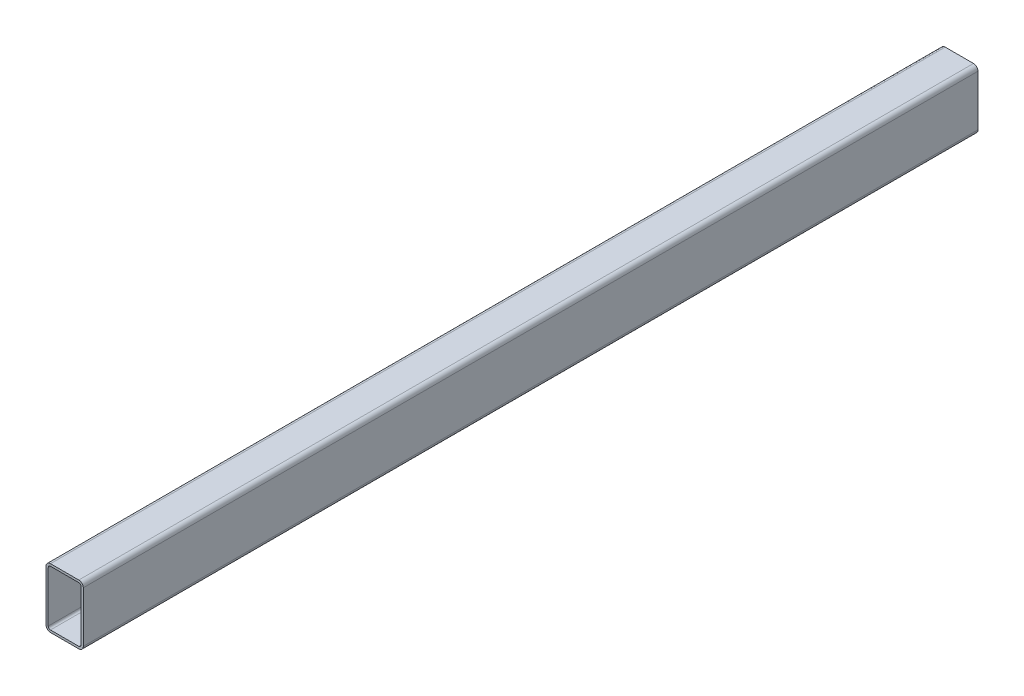
SolidWorks part; units mm, degrees
ref_plane "Front Plane" through (0, 0, 0) normal (0, 0, 1) x (1, 0, 0)
ref_plane "Top Plane" through (0, 0, 0) normal (0, 1, 0) x (1, 0, 0)
ref_plane "Right Plane" through (0, 0, 0) normal (1, 0, 0) x (0, 0, -1)
sketch "Sketch1" plane through (0, 0, 0) normal (0, 0, 1) x (1, 0, 0)
  line L0 (19, 37) -> (-19, 37)
  line L1 (19, -40) -> (-19, -40)
  line L2 (25, -34) -> (25, 34)
  line L3 (19, 40) -> (-19, 40)
  line L4 (-25, -34) -> (-25, 34)
  line L5 (25, -40) -> (-25, 40) construction
  line L6 (25, 40) -> (-25, -40) construction
  line L7 (-22, -34) -> (-22, 34)
  line L8 (19, -37) -> (-19, -37)
  line L9 (22, -34) -> (22, 34)
  arc A0 (-19, -40) -> (-25, -34) centre (-19, -34) cw
  arc A1 (19, -40) -> (25, -34) centre (19, -34) ccw
  arc A2 (25, 34) -> (19, 40) centre (19, 34) ccw
  arc A3 (-19, 40) -> (-25, 34) centre (-19, 34) ccw
  arc A4 (-19, 37) -> (-22, 34) centre (-19, 34) ccw
  arc A5 (-19, -37) -> (-22, -34) centre (-19, -34) cw
  arc A6 (19, -37) -> (22, -34) centre (19, -34) ccw
  arc A7 (22, 34) -> (19, 37) centre (19, 34) ccw
  point P0 (0, 0)
  dimension "D1" = 6
  dimension "D3" = 80
  dimension "D4" = 50
  dimension "D2" = 3
extrude "Boss-Extrude1" add sketch "Sketch1" along normal mid plane 1200
sketch "Sketch2" plane through (25, 0, 0) normal (1, 0, 0) x (0, 0, -1)
  line L0 (0, 197.5737) -> (0, -189.4858) construction
  line L1 (-600, -40) -> (600, -40) construction
  line L2 (-582, 22) -> (-568, 22) construction
  line L3 (-582, 22) -> (-582, -22) construction
  line L4 (-582, -22) -> (-568, -22) construction
  line L5 (-568, 22) -> (-568, -22) construction
  line L6 (-582, 22) -> (-568, -22) construction
  line L7 (-582, -22) -> (-568, 22) construction
  line L8 (-600, 40) -> (600, 40) construction
  line L9 (-582, 22) -> (-582, 40) construction
  line L10 (-582, 22) -> (-600, 22) construction
  line L11 (-600, -34) -> (-600, 34) construction
  line L12 (-600, 40) -> (-550, 40) construction
  line L13 (-600, 40) -> (-600, -40) construction
  line L14 (-600, -40) -> (-550, -40) construction
  line L15 (-550, 40) -> (-550, -40) construction
  line L16 (-575, -40) -> (-575, 40) construction
  line L17 (-600, 0) -> (-550, 0) construction
  circle A0 centre (-582, 22) radius 2.5
  circle A1 centre (-568, 22) radius 2.5
  circle A2 centre (-568, -22) radius 2.5
  circle A3 centre (-582, -22) radius 2.5
  circle A4 centre (-575, 0) radius 2.5
  circle A5 centre (568, -22) radius 2.5
  circle A6 centre (582, -22) radius 2.5
  circle A7 centre (575, 0) radius 2.5
  circle A8 centre (582, 22) radius 2.5
  circle A9 centre (568, 22) radius 2.5
  point P1 (-575, 0)
  dimension "D3" = 5
  dimension "D1" = 18
  dimension "D2" = 50
extrude "Cut-Extrude1" [suppressed] cut sketch "Sketch2" against normal through all
other "DeleteFace1" [suppressed]
equation "\"M5_tap\"=4.2mm\t\t\t\t\t\t\t' Below you can do mesurements as follows: cm, mm, ft, in, m, "
equation "\"M5_clearence\"=5.5mm"
equation "\"M6_tap\"=5mm"
equation "\"M6_clearence\"=6.6mm"
equation "\"work_area_width\"=1100mm"
equation "\"work_area_depth\"=900mm"
equation "\"D3@Sketch1\" = \"steel_base_width\""
equation "\"D4@Sketch1\" = \"steel_base_height\""
equation "\"D1@Sketch1\" = \"steel_base_radius\""
equation "\"D2@Sketch1\" = \"steel_base_wall_thickness\""
equation "\"D1@Boss-Extrude1\"=\"work_area_width\" + (\"steel_sides_height\"*2)"
equation "\"D1@Sketch2\" = \"steel_base_radius\" * 2 + 6mm"
equation "\"D2@Sketch2\"= \"steel_base_height\""
equation "\"D3@Sketch2\"=\"M6_tap\""
equation "\"steel_base_width\"=80mm"
equation "\"steel_base_height\"=50mm"
equation "\"steel_base_wall_thickness\"=3mm"
equation "\"steel_base_radius\"=6mm"
equation "\"steel_sides_width\"=80mm\t\t\t\t'this tube is rotated so flip width/height"
equation "\"steel_sides_height\"=50mm\t\t\t\t'this tube is rotated so flip width/height"
equation "\"steel_sides_wall_thickness\"=3mm"
equation "\"steel_sides_radius\"=6mm"
equation "\"steel_gantry_width\"=80mm\t\t\t\t'this tube is rotated so flip width/height"
equation "\"steel_gantry_height\"=50mm\t\t\t\t'this tube is rotated so flip width/height"
equation "\"steel_gantry_wall_thickness\"=3mm"
equation "\"steel_gantry_radius\"=6mm"
